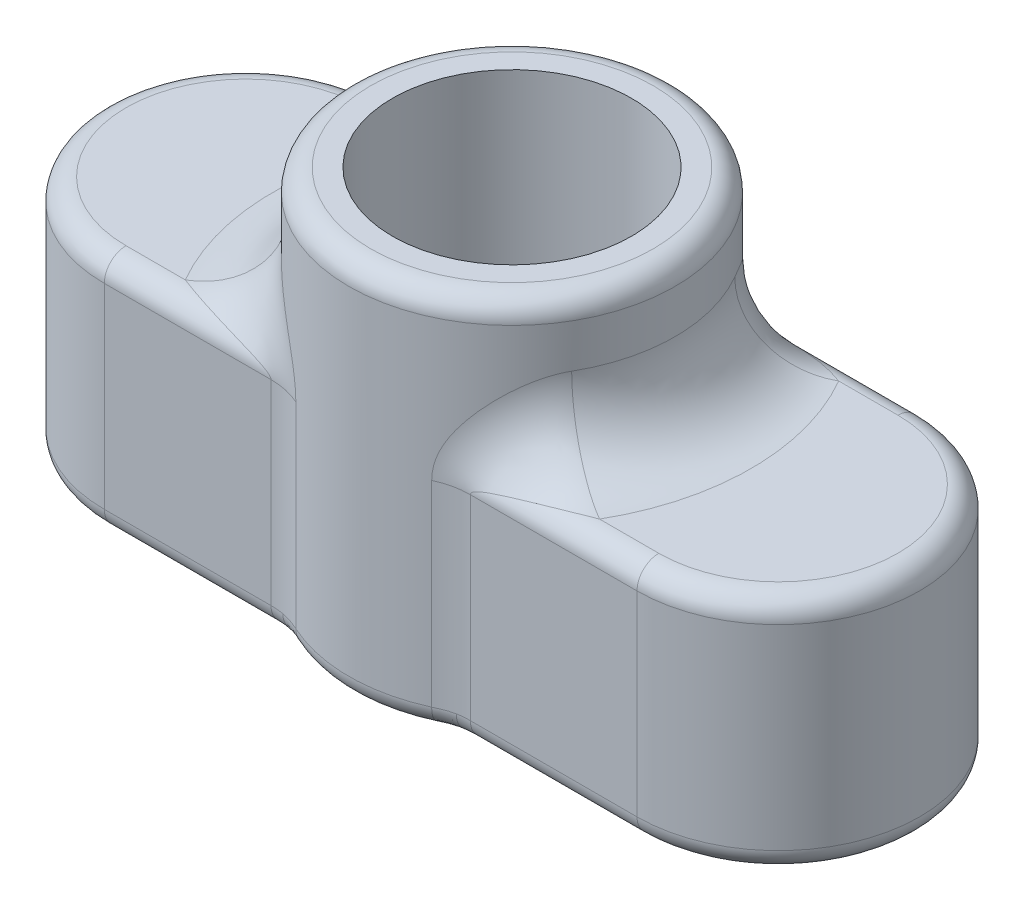
SolidWorks part; units mm, degrees
ref_plane "Front Plane" through (0, 0, 0) normal (0, 0, 1) x (1, 0, 0)
ref_plane "Top Plane" through (0, 0, 0) normal (0, 1, 0) x (1, 0, 0)
ref_plane "Right Plane" through (0, 0, 0) normal (1, 0, 0) x (0, 0, -1)
sketch "Sketch1" plane through (0, 0, 0) normal (0, 1, 0) x (1, 0, 0)
  line L0 (-24.5, 0) -> (24.5, 0) construction
  line L1 (-55, 0) -> (55, 0) construction
  line L2 (-24.5, 13) -> (-7.4833, 13)
  line L3 (-24.5, -13) -> (-7.4833, -13)
  line L4 (0, -55) -> (0, 55) construction
  line L5 (7.4833, 13) -> (24.5, 13)
  line L6 (7.4833, -13) -> (24.5, -13)
  arc A0 (-24.5, 13) -> (-24.5, -13) centre (-24.5, 0) ccw
  arc A1 (24.5, -13) -> (24.5, 13) centre (24.5, 0) ccw
  arc A2 (-7.4833, -13) -> (7.4833, -13) centre (0, 0) ccw
  arc A3 (7.4833, 13) -> (-7.4833, 13) centre (0, 0) ccw
  circle A4 centre (0, 0) radius 11
  point P5 (0, 0)
  point P13 (37.5, 0)
  point P14 (-37.5, 0)
  dimension "D2" = 37.5
  dimension "D4" = 30
  dimension "D5" = 22
  dimension "D6" = 15
  dimension "D1" = 26
  dimension "D3" = 37.5
extrude "Boss-Extrude1" add sketch "Sketch1" along normal blind 22
sketch "Sketch7" plane through (0, 0, 0) normal (0, 1, 0) x (1, 0, 0)
  circle A0 centre (0, 0) radius 15
  circle A1 centre (0, 0) radius 11
extrude "Boss-Extrude3" add sketch "Sketch7" along normal blind 35
sketch "Sketch8" plane through (0, 0, 0) normal (0, 1, 0) x (1, 0, 0)
  line L0 (-19.25, 0) -> (19.25, 0) construction
  arc A0 (-13.276, -2.4488) -> (13.276, -2.4488) centre (0, 0) ccw
  arc A1 (13.276, -2.4488) -> (13.276, 2.4488) centre (24, 0) ccw
  arc A2 (-13.276, 2.4488) -> (-13.276, -2.4488) centre (-24, 0) ccw
  arc A3 (13.276, 2.4488) -> (-13.276, 2.4488) centre (0, 0) ccw
  arc A4 (-24.5, 13) -> (-24.5, -13) centre (-24.5, 0) ccw construction
  point P13 (0, 0)
  dimension "D1" = 27
  dimension "D2" = 22
  dimension "D3" = 22
  dimension "D4" = 48
  dimension "D5" = 24
extrude "Cut-Extrude1" cut sketch "Sketch8" along normal blind 18
fillet "Fillet3" radius 2 6 edges at (-15.9917, 22, -13) (-37.5, 22, 0) (-15.9917, 22, 13) (15.9917, 22, -13) (37.5, 22, 0) (15.9917, 22, 13)
fillet "Fillet4" radius 7 5 edges at (7.4833, 10, -13) (8.1489, 21.2086, -12.5935) (7.4833, 10, 13) (7.7354, 20.756, 12.8516) (15, 22, 0)
fillet "Fillet5" radius 7 5 edges at (-7.4833, 10, 13) (-8.1489, 21.2086, 12.5935) (-7.4833, 10, -13) (-7.7354, 20.756, -12.8516) (-15, 22, 0)
fillet "Fillet6" radius 2 1 edges at (0, 35, 15)
fillet "Fillet7" radius 2 10 edges at (-37.5, 0, 0) (-16.8326, 0, -13) (-7.6727, 0, -13.1609) (7.6727, 0, -13.1609) (16.8326, 0, -13) (37.5, 0, 0) (16.8326, 0, 13) (7.6727, 0, 13.1609) (-7.6727, 0, 13.1609) (-16.8326, 0, 13)
